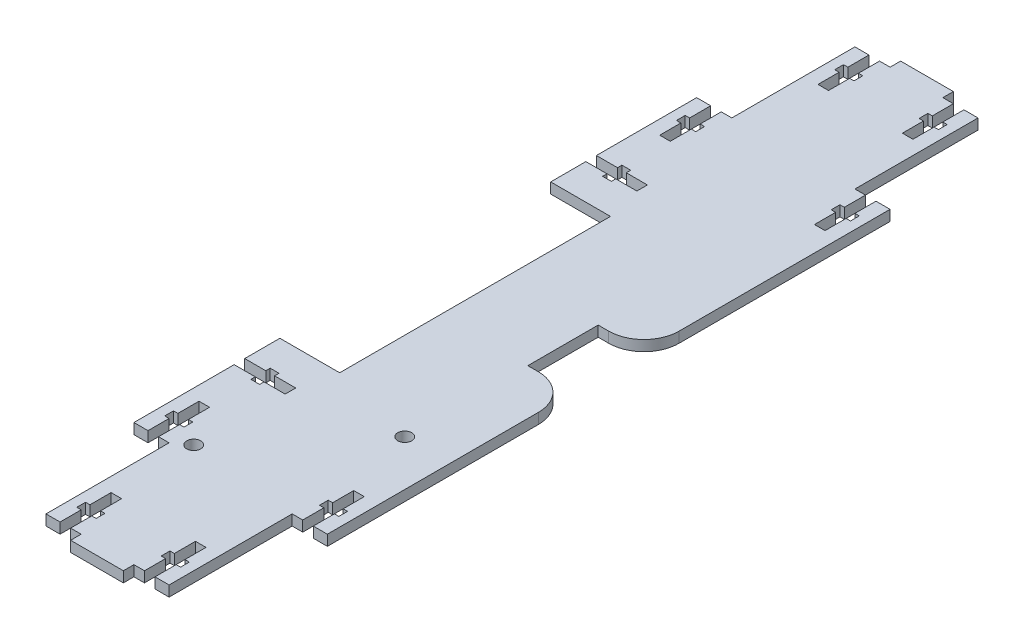
SolidWorks part; units mm, degrees
ref_plane "Спереди" through (0, 0, 0) normal (0, 0, 1) x (1, 0, 0)
ref_plane "Сверху" through (0, 0, 0) normal (0, 1, 0) x (1, 0, 0)
ref_plane "Справа" through (0, 0, 0) normal (1, 0, 0) x (0, 0, -1)
sketch "Эскиз1" plane through (0, 0, 0) normal (0, 1, 0) x (1, 0, 0)
  line L1 (-27.5, -80) -> (27.5, -80)
  line L2 (-27.5, -80) -> (-27.5, 80)
  line L3 (-27.5, 80) -> (27.5, 80)
  line L4 (27.5, -80) -> (27.5, 80)
  line L5 (-27.5, -80) -> (27.5, 80) construction
  line L6 (-27.5, 80) -> (27.5, -80) construction
  point P0 (0, 0)
  dimension "D1" = 55
  dimension "D2" = 160
extrude "Бобышка-Вытянуть1" add sketch "Эскиз1" along normal blind 3
sketch "Эскиз2" plane through (0, 0, -80) normal (0, 0, -1) x (-1, 0, 0)
  line L0 (-27.5, 0) -> (27.5, 0) construction
  line L1 (-17.5, 0) -> (17.5, 0)
  line L2 (-17.5, 0) -> (-17.5, 3)
  line L3 (-17.5, 3) -> (17.5, 3)
  line L4 (17.5, 0) -> (17.5, 3)
  line L5 (-27.5, 3) -> (27.5, 3) construction
  point P8 (0, 3)
  dimension "D1" = 35
  dimension "D2" = 27.5
extrude "Бобышка-Вытянуть2" add sketch "Эскиз2" along normal blind 35 and the other way blind 195
sketch "Эскиз3" plane through (0, 0, -115) normal (0, 0, -1) x (-1, 0, 0)
  line L0 (-17.5, 0) -> (17.5, 0) construction
  line L1 (-7.5, 0) -> (7.5, 0)
  line L2 (-7.5, 0) -> (-7.5, 3)
  line L3 (-7.5, 3) -> (7.5, 3)
  line L4 (7.5, 0) -> (7.5, 3)
  line L5 (17.5, 3) -> (-17.5, 3) construction
  point P8 (0, 0)
  dimension "D1" = 15
  dimension "D2" = 27.5
extrude "Бобышка-Вытянуть3" add sketch "Эскиз3" along normal blind 3 and the other way blind 233
sketch "Эскиз4" plane through (0, 3, 0) normal (0, 1, 0) x (1, 0, 0)
  line L0 (-23.5, 80) -> (-23.5, 74)
  line L1 (-13.5, 115) -> (-13.5, 109)
  line L2 (-23.5, 74) -> (-24.75, 74)
  line L3 (-24.75, 74) -> (-24.75, 71.5)
  line L4 (-24.75, 71.5) -> (-23.5, 71.5)
  line L5 (-23.5, 71.5) -> (-23.5, 65.5)
  line L6 (-23.5, 65.5) -> (-20.5, 65.5)
  line L7 (-20.5, 65.5) -> (-20.5, 71.5)
  line L8 (-20.5, 71.5) -> (-19.25, 71.5)
  line L9 (-19.25, 71.5) -> (-19.25, 74)
  line L10 (-19.25, 74) -> (-20.5, 74)
  line L11 (-20.5, 74) -> (-20.5, 80)
  line L12 (-13.5, 109) -> (-14.75, 109)
  line L13 (-20.5, 80) -> (-23.5, 80)
  line L14 (-14.75, 109) -> (-14.75, 106.5)
  line L15 (-14.75, 106.5) -> (-13.5, 106.5)
  line L16 (-13.5, 106.5) -> (-13.5, 100.5)
  line L17 (-13.5, 100.5) -> (-10.5, 100.5)
  line L18 (-10.5, 100.5) -> (-10.5, 106.5)
  line L19 (-10.5, 106.5) -> (-9.25, 106.5)
  line L20 (-9.25, 106.5) -> (-9.25, 109)
  line L21 (-9.25, 109) -> (-10.5, 109)
  line L22 (-10.5, 109) -> (-10.5, 115)
  line L23 (-10.5, 115) -> (-13.5, 115)
  line L24 (-17.5, 80) -> (-27.5, 80) construction
  line L25 (-17.5, 115) -> (-7.5, 115) construction
  line L26 (0, 118) -> (0, 75.6534) construction
  line L27 (-7.5, 118) -> (7.5, 118) construction
  line L28 (-27.5, 0) -> (22.9967, 0) construction
  line L29 (-27.5, 80) -> (-27.5, -80) construction
  line L30 (10.5, 115) -> (13.5, 115)
  line L31 (10.5, 109) -> (10.5, 115)
  line L32 (9.25, 109) -> (10.5, 109)
  line L33 (9.25, 106.5) -> (9.25, 109)
  line L34 (10.5, 106.5) -> (9.25, 106.5)
  line L35 (10.5, 100.5) -> (10.5, 106.5)
  line L36 (13.5, 100.5) -> (10.5, 100.5)
  line L37 (13.5, 106.5) -> (13.5, 100.5)
  line L38 (14.75, 106.5) -> (13.5, 106.5)
  line L39 (14.75, 109) -> (14.75, 106.5)
  line L40 (20.5, 80) -> (23.5, 80)
  line L41 (13.5, 109) -> (14.75, 109)
  line L42 (20.5, 74) -> (20.5, 80)
  line L43 (19.25, 74) -> (20.5, 74)
  line L44 (19.25, 71.5) -> (19.25, 74)
  line L45 (20.5, 71.5) -> (19.25, 71.5)
  line L46 (20.5, 65.5) -> (20.5, 71.5)
  line L47 (23.5, 65.5) -> (20.5, 65.5)
  line L48 (23.5, 71.5) -> (23.5, 65.5)
  line L49 (24.75, 71.5) -> (23.5, 71.5)
  line L50 (24.75, 74) -> (24.75, 71.5)
  line L51 (23.5, 74) -> (24.75, 74)
  line L52 (13.5, 115) -> (13.5, 109)
  line L53 (23.5, 80) -> (23.5, 74)
  line L54 (-10.5, -115) -> (-13.5, -115)
  line L55 (-10.5, -109) -> (-10.5, -115)
  line L56 (-9.25, -109) -> (-10.5, -109)
  line L57 (-9.25, -106.5) -> (-9.25, -109)
  line L58 (-10.5, -106.5) -> (-9.25, -106.5)
  line L59 (-10.5, -100.5) -> (-10.5, -106.5)
  line L60 (-13.5, -100.5) -> (-10.5, -100.5)
  line L61 (-13.5, -106.5) -> (-13.5, -100.5)
  line L62 (-14.75, -106.5) -> (-13.5, -106.5)
  line L63 (-14.75, -109) -> (-14.75, -106.5)
  line L64 (-13.5, -109) -> (-14.75, -109)
  line L65 (-13.5, -115) -> (-13.5, -109)
  line L66 (13.5, -115) -> (13.5, -109)
  line L67 (13.5, -109) -> (14.75, -109)
  line L68 (14.75, -109) -> (14.75, -106.5)
  line L69 (14.75, -106.5) -> (13.5, -106.5)
  line L70 (13.5, -106.5) -> (13.5, -100.5)
  line L71 (13.5, -100.5) -> (10.5, -100.5)
  line L72 (10.5, -100.5) -> (10.5, -106.5)
  line L73 (10.5, -106.5) -> (9.25, -106.5)
  line L74 (9.25, -106.5) -> (9.25, -109)
  line L75 (9.25, -109) -> (10.5, -109)
  line L76 (10.5, -109) -> (10.5, -115)
  line L77 (10.5, -115) -> (13.5, -115)
  line L78 (-20.5, -80) -> (-23.5, -80)
  line L79 (-20.5, -74) -> (-20.5, -80)
  line L80 (-19.25, -74) -> (-20.5, -74)
  line L81 (-19.25, -71.5) -> (-19.25, -74)
  line L82 (-20.5, -71.5) -> (-19.25, -71.5)
  line L83 (-20.5, -65.5) -> (-20.5, -71.5)
  line L84 (-23.5, -65.5) -> (-20.5, -65.5)
  line L85 (-23.5, -71.5) -> (-23.5, -65.5)
  line L86 (-24.75, -71.5) -> (-23.5, -71.5)
  line L87 (-24.75, -74) -> (-24.75, -71.5)
  line L88 (-23.5, -74) -> (-24.75, -74)
  line L89 (-23.5, -80) -> (-23.5, -74)
  line L90 (23.5, -80) -> (23.5, -74)
  line L91 (23.5, -74) -> (24.75, -74)
  line L92 (24.75, -74) -> (24.75, -71.5)
  line L93 (24.75, -71.5) -> (23.5, -71.5)
  line L94 (23.5, -71.5) -> (23.5, -65.5)
  line L95 (23.5, -65.5) -> (20.5, -65.5)
  line L96 (20.5, -65.5) -> (20.5, -71.5)
  line L97 (20.5, -71.5) -> (19.25, -71.5)
  line L98 (19.25, -71.5) -> (19.25, -74)
  line L99 (19.25, -74) -> (20.5, -74)
  line L100 (20.5, -74) -> (20.5, -80)
  line L101 (20.5, -80) -> (23.5, -80)
  point P29 (-22, 80)
  point P112 (-12, 115)
  dimension "D1" = 3
  dimension "D2" = 5.5
  dimension "D3" = 6
  dimension "D4" = 2.5
  dimension "D5" = 3
  dimension "D6" = 5.5
  dimension "D7" = 6
  dimension "D8" = 2.5
  dimension "D9" = 4.5
  dimension "D10" = 4
  dimension "D11" = 4.5
extrude "Вырез-Вытянуть1" cut sketch "Эскиз4" against normal blind 3
sketch "Эскиз5" plane through (0, 3, 0) normal (0, 1, 0) x (1, 0, 0)
  line L0 (-27.5, 51.5) -> (-21.5, 51.5)
  line L1 (-21.5, 51.5) -> (-21.5, 52.75)
  line L2 (-21.5, 52.75) -> (-19, 52.75)
  line L3 (-19, 52.75) -> (-19, 51.5)
  line L4 (-19, 51.5) -> (-13, 51.5)
  line L5 (-13, 51.5) -> (-13, 48.5)
  line L6 (-13, 48.5) -> (-19, 48.5)
  line L7 (-19, 48.5) -> (-19, 47.25)
  line L8 (-19, 47.25) -> (-21.5, 47.25)
  line L9 (-21.5, 47.25) -> (-21.5, 48.5)
  line L10 (-21.5, 48.5) -> (-27.5, 48.5)
  line L11 (-27.5, 48.5) -> (-27.5, 51.5)
  line L12 (-27.5, 80) -> (-27.5, -80) construction
  line L13 (-27.5, 0) -> (-6.9327, 0) construction
  line L14 (-27.5, -48.5) -> (-27.5, -51.5)
  line L15 (-21.5, -48.5) -> (-27.5, -48.5)
  line L16 (-21.5, -47.25) -> (-21.5, -48.5)
  line L17 (-19, -47.25) -> (-21.5, -47.25)
  line L18 (-19, -48.5) -> (-19, -47.25)
  line L19 (-13, -48.5) -> (-19, -48.5)
  line L20 (-13, -51.5) -> (-13, -48.5)
  line L21 (-19, -51.5) -> (-13, -51.5)
  line L22 (-19, -52.75) -> (-19, -51.5)
  line L23 (-21.5, -52.75) -> (-19, -52.75)
  line L24 (-21.5, -51.5) -> (-21.5, -52.75)
  line L25 (-27.5, -51.5) -> (-21.5, -51.5)
  point P30 (-27.5, 50)
  dimension "D1" = 3
  dimension "D2" = 6
  dimension "D3" = 2.5
  dimension "D4" = 5.5
  dimension "D5" = 50
extrude "Вырез-Вытянуть2" cut sketch "Эскиз5" against normal blind 3
sketch "Эскиз6" plane through (-27.5, 0, 0) normal (-1, 0, 0) x (0, 0, 1)
  line L0 (-48.5, 3) -> (48.5, 3) construction
  line L1 (-38.5, 3) -> (38.5, 3)
  line L2 (-38.5, 3) -> (-38.5, 0)
  line L3 (-38.5, 0) -> (38.5, 0)
  line L4 (38.5, 3) -> (38.5, 0)
  line L5 (-48.5, 0) -> (48.5, 0) construction
  point P8 (0, 0)
  dimension "D1" = 77
extrude "Вырез-Вытянуть3" cut sketch "Эскиз6" against normal blind 17
sketch "Эскиз8" plane through (0, 3, 0) normal (0, 1, 0) x (1, 0, 0)
  circle A0 centre (-13.5, -77) radius 2
  circle A1 centre (14.5, -45) radius 2
  dimension "D1" = 4
  dimension "D2" = 3
  dimension "D3" = 4
  dimension "D4" = 28
  dimension "D5" = 32
extrude "Вырез-Вытянуть4" cut sketch "Эскиз8" against normal blind 3
sketch "Эскиз9" plane through (0, 3, 0) normal (0, 1, 0) x (1, 0, 0)
  line L0 (27.5, -80) -> (27.5, 80) construction
  line L1 (27.5, -10) -> (14.5, -10)
  line L2 (27.5, -10) -> (27.5, 10)
  line L3 (27.5, 10) -> (14.5, 10)
  line L4 (14.5, -10) -> (14.5, 10)
  line L5 (-10.5, -38.5) -> (-10.5, 38.5) construction
  point P8 (27.5, 0)
  point P9 (27.5, 0)
  dimension "D1" = 20
  dimension "D2" = 25
extrude "Вырез-Вытянуть5" cut sketch "Эскиз9" against normal blind 3
fillet "Скругление1" radius 10 2 edges at (27.5, 1.5, 10) (27.5, 1.5, -10)
